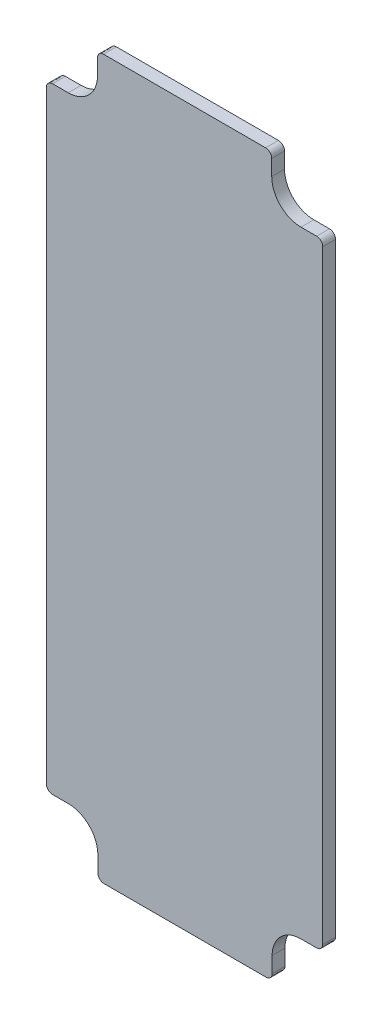
SolidWorks part; units mm, degrees
ref_plane "Front Plane" through (0, 0, 0) normal (0, 0, 1) x (1, 0, 0)
ref_plane "Top Plane" through (0, 0, 0) normal (0, 1, 0) x (1, 0, 0)
ref_plane "Right Plane" through (0, 0, 0) normal (1, 0, 0) x (0, 0, -1)
sketch3d "3DSketch1" plane through (0, 0, 0) normal (0, 0, 1) x (1, 0, 0)
  dimension "D1" = 5
sketch "Sketch2" plane through (0, 0, 5) normal (0, 0, 1) x (1, 0, 0)
  line L0 (-18.9245, -40.3) -> (-18.9245, 40.3)
  line L1 (13.25, -45.9745) -> (-13.25, -45.9745)
  line L2 (-13.25, 45.9745) -> (13.25, 45.9745)
  line L3 (18.9245, 40.3) -> (18.9245, -40.3)
  line L4 (-16.1749, 37.9745) -> (-14.25, 37.9745)
  line L5 (10.9245, 43.2249) -> (10.9245, 41.3)
  line L6 (17.1745, 36.9749) -> (17.1745, -37.0249)
  line L7 (14.25, 37.9745) -> (16.1749, 37.9745)
  line L8 (-9.9249, 44.2245) -> (9.9249, 44.2245)
  line L9 (-10.9245, 41.3) -> (-10.9245, 43.2249)
  line L10 (-17.1745, -36.9249) -> (-17.1745, 36.9749)
  line L11 (-14.25, -37.9245) -> (-16.1749, -37.9245)
  line L12 (-10.8745, -43.2249) -> (-10.8745, -41.3)
  line L13 (9.9749, -44.2245) -> (-9.8749, -44.2245)
  line L14 (10.9745, -41.3) -> (10.9745, -43.2249)
  line L15 (16.1749, -38.0245) -> (14.25, -38.0245)
  line L16 (16.1749, -38.0245) -> (14.25, -38.0245) construction
  line L17 (10.9745, -41.3) -> (10.9745, -43.2249) construction
  line L18 (9.9749, -44.2245) -> (-9.8749, -44.2245) construction
  line L19 (-10.8745, -43.2249) -> (-10.8745, -41.3) construction
  line L20 (-14.25, -37.9245) -> (-16.1749, -37.9245) construction
  line L21 (-17.1745, -36.9249) -> (-17.1745, 36.9749) construction
  line L22 (-10.9245, 41.3) -> (-10.9245, 43.2249) construction
  line L23 (-9.9249, 44.2245) -> (9.9249, 44.2245) construction
  line L24 (14.25, 37.9745) -> (16.1749, 37.9745) construction
  line L25 (17.1745, 36.9749) -> (17.1745, -37.0249) construction
  line L26 (10.9245, 43.2249) -> (10.9245, 41.3) construction
  line L27 (-16.1749, 37.9745) -> (-14.25, 37.9745) construction
  line L28 (18.9245, 40.3) -> (18.9245, -40.3) construction
  line L29 (-13.25, 45.9745) -> (13.25, 45.9745) construction
  line L30 (13.25, -45.9745) -> (-13.25, -45.9745) construction
  line L31 (-18.9245, -40.3) -> (-18.9245, 40.3) construction
  line L32 (-16.9205, -36.9249) -> (-16.9205, 36.9749)
  line L33 (-16.1749, 37.7205) -> (-14.25, 37.7205)
  line L34 (-10.6705, 41.3) -> (-10.6705, 43.2249)
  line L35 (-9.9249, 43.9705) -> (9.9249, 43.9705)
  line L36 (10.6705, 43.2249) -> (10.6705, 41.3)
  line L37 (14.25, 37.7205) -> (16.1749, 37.7205)
  line L38 (16.9205, 36.9749) -> (16.9205, -37.0249)
  line L39 (16.1749, -37.7705) -> (14.25, -37.7705)
  line L40 (10.7205, -41.3) -> (10.7205, -43.2249)
  line L41 (9.9749, -43.9705) -> (-9.8749, -43.9705)
  line L42 (-10.6205, -43.2249) -> (-10.6205, -41.3)
  line L43 (-14.25, -37.6705) -> (-16.1749, -37.6705)
  arc A0 (-18.9245, -40.3) -> (-13.25, -45.9745) centre (-13.25, -40.3) ccw
  arc A1 (-13.25, 45.9745) -> (-18.9245, 40.3) centre (-13.25, 40.3) ccw
  arc A2 (18.9245, 40.3) -> (13.25, 45.9745) centre (13.25, 40.3) ccw
  arc A3 (13.25, -45.9745) -> (18.9245, -40.3) centre (13.25, -40.3) ccw
  arc A4 (-14.25, 37.9745) -> (-10.9245, 41.3) centre (-14.25, 41.3) ccw
  arc A5 (10.9245, 41.3) -> (14.25, 37.9745) centre (14.25, 41.3) ccw
  circle A6 centre (14.25, -41.3) radius 1.321
  circle A7 centre (-14.25, 41.3) radius 1.321
  circle A8 centre (-14.25, -41.3) radius 1.321
  circle A9 centre (14.25, 41.3) radius 1.321
  arc A10 (-10.8745, -41.3) -> (-14.25, -37.9245) centre (-14.25, -41.3) ccw
  arc A11 (14.25, -38.0245) -> (10.9745, -41.3) centre (14.25, -41.3) ccw
  arc A12 (14.25, -38.0245) -> (10.9745, -41.3) centre (14.25, -41.3) ccw construction
  arc A13 (-10.8745, -41.3) -> (-14.25, -37.9245) centre (-14.25, -41.3) ccw construction
  circle A14 centre (14.25, 41.3) radius 1.321 construction
  circle A15 centre (-14.25, -41.3) radius 1.321 construction
  circle A16 centre (-14.25, 41.3) radius 1.321 construction
  circle A17 centre (14.25, -41.3) radius 1.321 construction
  arc A18 (10.9245, 41.3) -> (14.25, 37.9745) centre (14.25, 41.3) ccw construction
  arc A19 (-14.25, 37.9745) -> (-10.9245, 41.3) centre (-14.25, 41.3) ccw construction
  arc A20 (13.25, -45.9745) -> (18.9245, -40.3) centre (13.25, -40.3) ccw construction
  arc A21 (18.9245, 40.3) -> (13.25, 45.9745) centre (13.25, 40.3) ccw construction
  arc A22 (-13.25, 45.9745) -> (-18.9245, 40.3) centre (-13.25, 40.3) ccw construction
  arc A23 (-18.9245, -40.3) -> (-13.25, -45.9745) centre (-13.25, -40.3) ccw construction
  arc A24 (-14.25, 37.7205) -> (-10.6705, 41.3) centre (-14.25, 41.3) ccw
  arc A25 (10.6705, 41.3) -> (14.25, 37.7205) centre (14.25, 41.3) ccw
  arc A26 (14.25, -37.7705) -> (10.7205, -41.3) centre (14.25, -41.3) ccw
  arc A27 (-10.6205, -41.3) -> (-14.25, -37.6705) centre (-14.25, -41.3) ccw
  spline S0 degree 3 poles (16.1749, 37.9745) (16.7605, 37.9745) (17.1745, 37.5605) (17.1745, 36.9749) knots 0 0 0 0 1 1 1 1 weights 1 0.804899 0.804899 1
  spline S1 degree 3 poles (9.9249, 44.2245) (10.5105, 44.2245) (10.9245, 43.8105) (10.9245, 43.2249) knots 0 0 0 0 1 1 1 1 weights 1 0.804899 0.804899 1
  spline S2 degree 3 poles (-10.9245, 43.2249) (-10.9245, 43.8105) (-10.5105, 44.2245) (-9.9249, 44.2245) knots 0 0 0 0 1 1 1 1 weights 1 0.804899 0.804899 1
  spline S3 degree 3 poles (-17.1745, 36.9749) (-17.1745, 37.5605) (-16.7605, 37.9745) (-16.1749, 37.9745) knots 0 0 0 0 1 1 1 1 weights 1 0.804899 0.804899 1
  spline S4 degree 3 poles (-16.1749, -37.9245) (-16.7605, -37.9245) (-17.1745, -37.5105) (-17.1745, -36.9249) knots 0 0 0 0 1 1 1 1 weights 1 0.804899 0.804899 1
  spline S5 degree 3 poles (-9.8749, -44.2245) (-10.4605, -44.2245) (-10.8745, -43.8105) (-10.8745, -43.2249) knots 0 0 0 0 1 1 1 1 weights 1 0.804899 0.804899 1
  spline S6 degree 3 poles (10.9745, -43.2249) (10.9745, -43.8105) (10.5605, -44.2245) (9.9749, -44.2245) knots 0 0 0 0 1 1 1 1 weights 1 0.804899 0.804899 1
  spline S7 degree 3 poles (17.1745, -37.0249) (17.1745, -37.6105) (16.7605, -38.0245) (16.1749, -38.0245) knots 0 0 0 0 1 1 1 1 weights 1 0.804899 0.804899 1
  spline S8 degree 3 poles (17.1745, -37.0249) (17.1745, -37.6105) (16.7605, -38.0245) (16.1749, -38.0245) knots 0 0 0 0 1 1 1 1 weights 1 0.804899 0.804899 1 construction
  spline S9 degree 3 poles (10.9745, -43.2249) (10.9745, -43.8105) (10.5605, -44.2245) (9.9749, -44.2245) knots 0 0 0 0 1 1 1 1 weights 1 0.804899 0.804899 1 construction
  spline S10 degree 3 poles (-9.8749, -44.2245) (-10.4605, -44.2245) (-10.8745, -43.8105) (-10.8745, -43.2249) knots 0 0 0 0 1 1 1 1 weights 1 0.804899 0.804899 1 construction
  spline S11 degree 3 poles (-16.1749, -37.9245) (-16.7605, -37.9245) (-17.1745, -37.5105) (-17.1745, -36.9249) knots 0 0 0 0 1 1 1 1 weights 1 0.804899 0.804899 1 construction
  spline S12 degree 3 poles (-17.1745, 36.9749) (-17.1745, 37.5605) (-16.7605, 37.9745) (-16.1749, 37.9745) knots 0 0 0 0 1 1 1 1 weights 1 0.804899 0.804899 1 construction
  spline S13 degree 3 poles (-10.9245, 43.2249) (-10.9245, 43.8105) (-10.5105, 44.2245) (-9.9249, 44.2245) knots 0 0 0 0 1 1 1 1 weights 1 0.804899 0.804899 1 construction
  spline S14 degree 3 poles (9.9249, 44.2245) (10.5105, 44.2245) (10.9245, 43.8105) (10.9245, 43.2249) knots 0 0 0 0 1 1 1 1 weights 1 0.804899 0.804899 1 construction
  spline S15 degree 3 poles (16.1749, 37.9745) (16.7605, 37.9745) (17.1745, 37.5605) (17.1745, 36.9749) knots 0 0 0 0 1 1 1 1 weights 1 0.804899 0.804899 1 construction
  spline S16 degree 1 poles (-16.9205, 36.9749) (-16.1749, 37.7205) knots 0 0 1 1 construction
  spline S17 degree 1 poles (-10.6705, 43.2249) (-9.9249, 43.9705) knots 0 0 1 1 construction
  spline S18 degree 1 poles (9.9249, 43.9705) (10.6705, 43.2249) knots 0 0 1 1 construction
  spline S19 degree 1 poles (16.1749, 37.7205) (16.9205, 36.9749) knots 0 0 1 1 construction
  spline S20 degree 1 poles (16.9205, -37.0249) (16.1749, -37.7705) knots 0 0 1 1 construction
  spline S21 degree 1 poles (10.7205, -43.2249) (9.9749, -43.9705) knots 0 0 1 1 construction
  spline S22 degree 1 poles (-9.8749, -43.9705) (-10.6205, -43.2249) knots 0 0 1 1 construction
  spline S23 degree 1 poles (-16.1749, -37.6705) (-16.9205, -36.9249) knots 0 0 1 1 construction
  spline S24 degree 3 poles (-16.9205, 36.9749) (-16.9205, 37.068) (-16.8885, 37.2502) (-16.7186, 37.5186) (-16.4502, 37.6885) (-16.268, 37.7205) (-16.1749, 37.7205) knots 0 0 0 0 0.25 0.5 0.75 1 1 1 1
  spline S25 degree 3 poles (-10.6705, 43.2249) (-10.6705, 43.318) (-10.6385, 43.5002) (-10.4686, 43.7686) (-10.2002, 43.9385) (-10.018, 43.9705) (-9.9249, 43.9705) knots 0 0 0 0 0.25 0.5 0.75 1 1 1 1
  spline S26 degree 3 poles (9.9249, 43.9705) (10.018, 43.9705) (10.2002, 43.9385) (10.4686, 43.7686) (10.6385, 43.5002) (10.6705, 43.318) (10.6705, 43.2249) knots 0 0 0 0 0.25 0.5 0.75 1 1 1 1
  spline S27 degree 3 poles (16.1749, 37.7205) (16.268, 37.7205) (16.4502, 37.6885) (16.7186, 37.5186) (16.8885, 37.2502) (16.9205, 37.068) (16.9205, 36.9749) knots 0 0 0 0 0.25 0.5 0.75 1 1 1 1
  spline S28 degree 3 poles (16.9205, -37.0249) (16.9205, -37.118) (16.8885, -37.3002) (16.7186, -37.5686) (16.4502, -37.7385) (16.268, -37.7705) (16.1749, -37.7705) knots 0 0 0 0 0.25 0.5 0.75 1 1 1 1
  spline S29 degree 3 poles (10.7205, -43.2249) (10.7205, -43.318) (10.6885, -43.5002) (10.5186, -43.7686) (10.2502, -43.9385) (10.068, -43.9705) (9.9749, -43.9705) knots 0 0 0 0 0.25 0.5 0.75 1 1 1 1
  spline S30 degree 3 poles (-9.8749, -43.9705) (-9.968, -43.9705) (-10.1502, -43.9385) (-10.4186, -43.7686) (-10.5885, -43.5002) (-10.6205, -43.318) (-10.6205, -43.2249) knots 0 0 0 0 0.25 0.5 0.75 1 1 1 1
  spline S31 degree 3 poles (-16.1749, -37.6705) (-16.268, -37.6705) (-16.4502, -37.6385) (-16.7186, -37.4686) (-16.8885, -37.2002) (-16.9205, -37.018) (-16.9205, -36.9249) knots 0 0 0 0 0.25 0.5 0.75 1 1 1 1
  dimension "D1" = 0.254
extrude "Boss-Extrude1" add sketch "Sketch2" along normal blind 1.57
